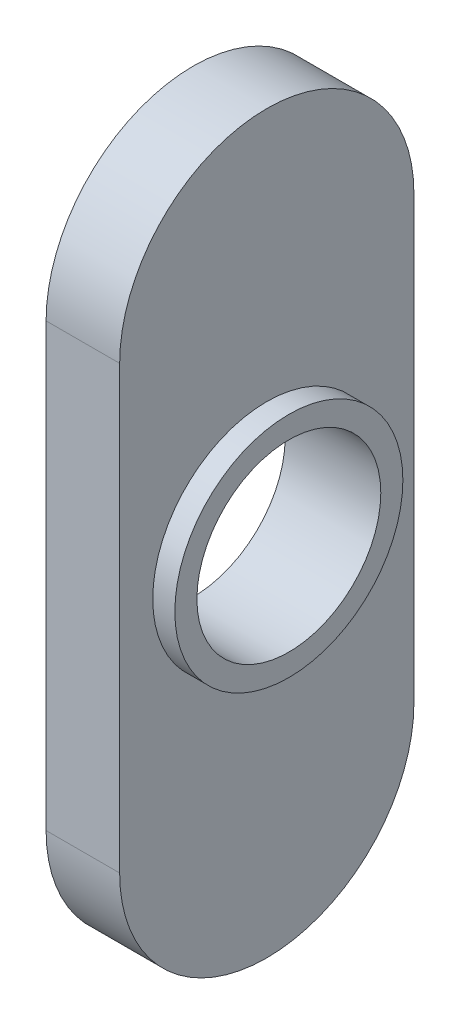
SolidWorks part; units mm, degrees
material "Plain Carbon Steel"
ref_plane "Front" through (0, 0, 0) normal (0, 0, 1) x (1, 0, 0)
ref_plane "Top" through (0, 0, 0) normal (0, 1, 0) x (1, 0, 0)
ref_plane "Right" through (0, 0, 0) normal (1, 0, 0) x (0, 0, -1)
ref_axis "Axis1" through (0, 0, 55) along (0, 0, -1)
sketch "Sketch1" plane through (0, 0, 0) normal (1, 0, 0) x (0, 0, -1)
  line L0 (0, 7.62) -> (0, -7.62) construction
  line L1 (5.08, 7.62) -> (5.08, -7.62)
  line L2 (-5.08, 7.62) -> (-5.08, -7.62)
  arc A0 (5.08, 7.62) -> (-5.08, 7.62) centre (0, 7.62) ccw
  arc A1 (-5.08, -7.62) -> (5.08, -7.62) centre (0, -7.62) ccw
  circle A2 centre (0, 0) radius 3.175
  point P2 (0, 0)
  dimension "D1" = 6.35
  dimension "D2" = 5.08
  dimension "D3" = 15.24
extrude "Boss-Extrude1" add sketch "Sketch1" along normal blind 2.54
sketch "Sketch2" plane through (2.54, 0, 0) normal (1, 0, 0) x (0, 0, -1)
  circle A0 centre (0, 0) radius 3.175 construction
  circle A1 centre (0, 0) radius 3.175
  circle A2 centre (0, 0) radius 3.937
  dimension "D1" = 0.762
extrude "Boss-Extrude2" add sketch "Sketch2" along normal blind 0.762
